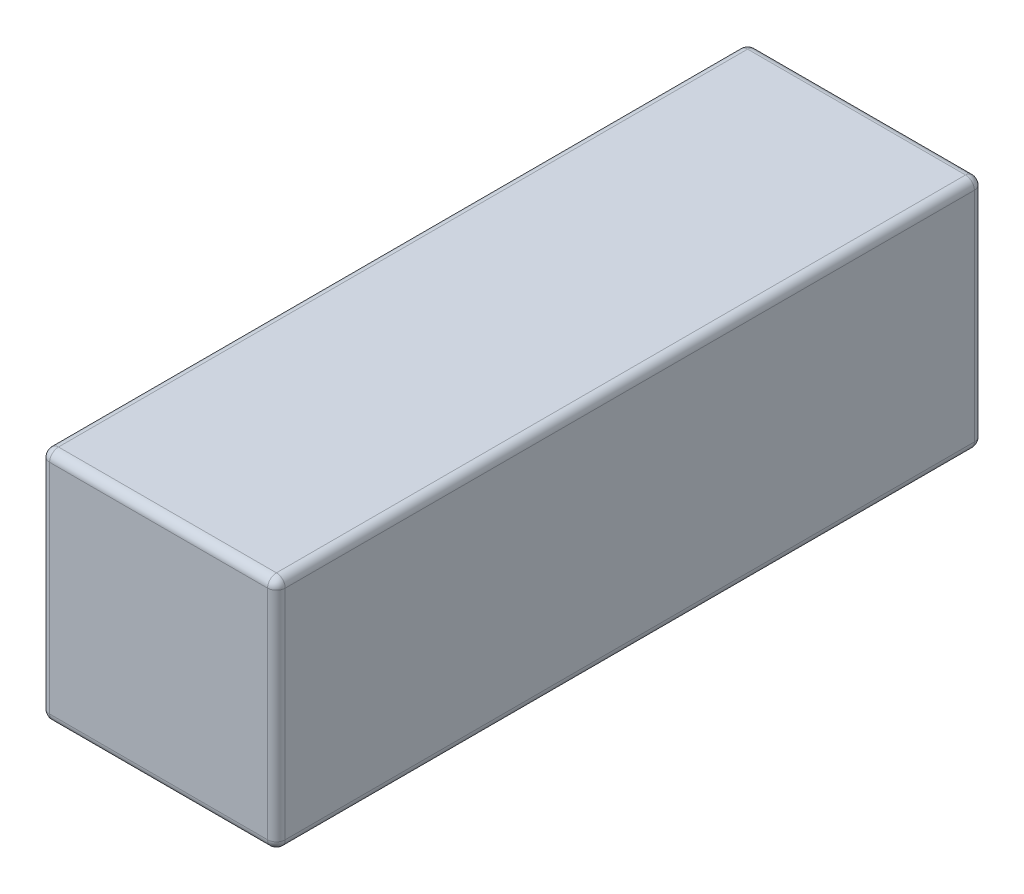
SolidWorks part; units mm, degrees
ref_plane "Front Plane" through (0, 0, 0) normal (0, 0, 1) x (1, 0, 0)
ref_plane "Top Plane" through (0, 0, 0) normal (0, 1, 0) x (1, 0, 0)
ref_plane "Right Plane" through (0, 0, 0) normal (1, 0, 0) x (0, 0, -1)
sketch "Sketch1" plane through (0, 0, 0) normal (0, 0, 1) x (1, 0, 0)
  line L3 (2, -2) -> (-2, -2)
  line L4 (2, -2) -> (2, 2)
  line L5 (2, 2) -> (-2, 2)
  line L6 (-2, -2) -> (-2, 2)
  line L7 (2, -2) -> (-2, 2) construction
  line L8 (2, 2) -> (-2, -2) construction
  point P0 (0, 0)
  dimension "Width" = 4
  dimension "Height" = 4
sketch "Sketch2" plane through (0, 0, 0) normal (1, 0, 0) x (0, 0, -1)
  line L2 (6, -2) -> (-6, -2)
  line L3 (6, -2) -> (6, 2)
  line L4 (6, 2) -> (-6, 2)
  line L5 (-6, -2) -> (-6, 2)
  line L6 (6, -2) -> (-6, 2) construction
  line L7 (6, 2) -> (-6, -2) construction
  point P0 (0, 0)
  point P4 (0, 0)
  dimension "Length" = 12
sketch "Sketch3" plane through (0, 0, 0) normal (0, 0, 1) x (1, 0, 0)
  line L0 (2, -2) -> (2, 2) construction
  line L5 (2, -2) -> (-2, -2) construction
  line L6 (-2, -2) -> (-2, 2) construction
  line L7 (2, 2) -> (-2, 2) construction
  line L8 (2, -2) -> (2, 2)
  line L9 (2, -2) -> (-2, -2)
  line L10 (-2, -2) -> (-2, 2)
  line L11 (2, 2) -> (-2, 2)
extrude "Boss-Extrude1" add sketch "Sketch3" along normal up to vertex (6 mm away) and the other way up to vertex (6 mm away) up to point (0, 2, 6) other way up to point (0, 2, -6)
fillet "Fillet2" radius 0.15 12 edges at (-2, 0, -6) (0, -2, -6) (-2, 2, 0) (0, 2, -6) (2, 2, 0) (2, 0, -6) (2, -2, 0) (-2, 0, 6) (0, 2, 6) (2, 0, 6) (0, -2, 6) (-2, -2, 0)
ref_plane "Contact Plane 1" through (0, 0, 6) normal (0, 0, 1) x (1, 0, 0)
ref_plane "Contact Plane 2" through (0, 0, -6) normal (0, 0, 1) x (1, 0, 0)
ref_axis "Center Axis 1" through (0, 0, -4.4) along (0, 0, 1)
